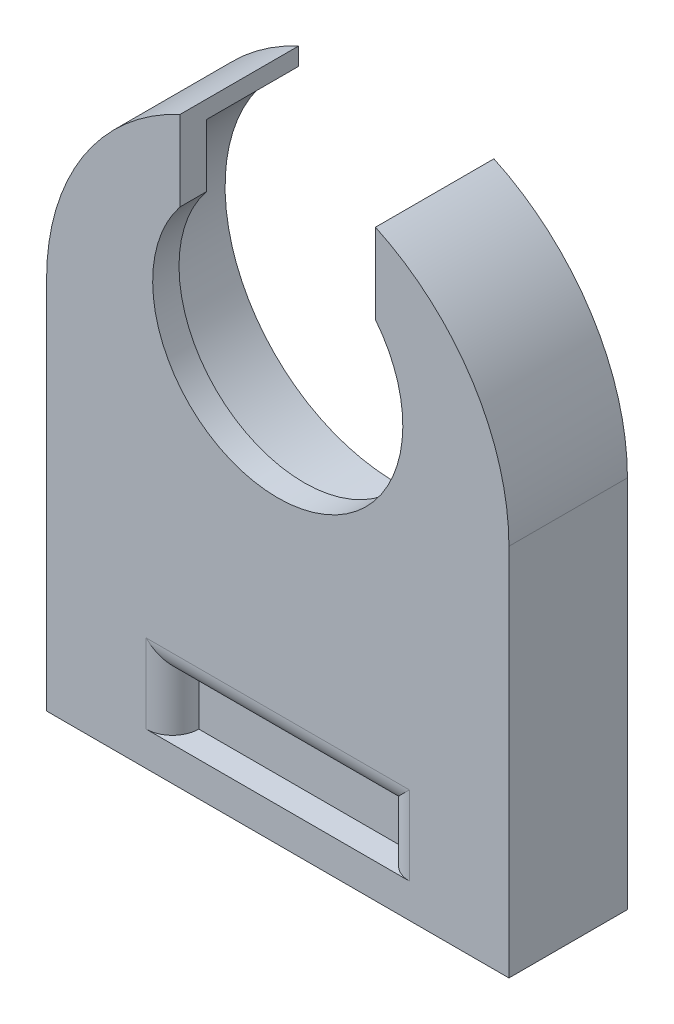
SolidWorks part; units mm, degrees
ref_plane "Front Plane" through (0, 0, 0) normal (0, 0, 1) x (1, 0, 0)
ref_plane "Top Plane" through (0, 0, 0) normal (0, 1, 0) x (1, 0, 0)
ref_plane "Right Plane" through (0, 0, 0) normal (1, 0, 0) x (0, 0, -1)
sketch "Sketch1" plane through (0, 0, 0) normal (0, 0, 1) x (1, 0, 0)
  line L0 (5.32, 14.0026) -> (5.32, 14.6195)
  line L1 (0, 0) -> (17.56, 0)
  line L2 (0, 0) -> (0, 6.55)
  line L3 (0, 6.55) -> (17.56, 6.55)
  line L4 (17.56, 0) -> (17.56, 6.55)
  line L6 (12.24, 14.0026) -> (12.24, 14.6195)
  arc A0 (5.32, 14.6195) -> (0, 6.55) centre (8.78, 6.55) ccw
  arc A1 (5.32, 14.0026) -> (12.24, 14.0026) centre (8.78, 8.5) ccw
  arc A2 (17.56, 6.55) -> (12.24, 14.6195) centre (8.78, 6.55) ccw
  dimension "D4" = 13
  dimension "D1" = 17.56
  dimension "D2" = 6.55
  dimension "D5" = 1.95
  dimension "D6" = 5.32
extrude "Boss-Extrude1" add sketch "Sketch1" along normal blind 3.5 contours A1 L3 L2 L1 L4 | A1 L0 A0 L3 | L3 A2 L6 A1 region at (1.98, 9.9073, 0) region at (8.78, 1.8126, 0) region at (15.58, 9.9073, 0)
sketch "Sketch3" plane through (0, 0, 3.5) normal (0, 0, 1) x (1, 0, 0)
  line L5 (5.32, 14.0026) -> (5.32, 14.6195)
  line L6 (0, 6.55) -> (0, 0)
  line L7 (0, 0) -> (17.56, 0)
  line L8 (17.56, 0) -> (17.56, 6.55)
  line L9 (12.24, 14.6195) -> (12.24, 14.0026)
  line L10 (5.32, 14.0026) -> (5.32, 14.6195)
  line L11 (0, 6.55) -> (0, 0)
  line L12 (0, 0) -> (17.56, 0)
  line L13 (17.56, 0) -> (17.56, 6.55)
  line L14 (12.24, 14.6195) -> (12.24, 14.0026)
  line L15 (0, 0) -> (17.56, 0)
  line L16 (17.56, 6.55) -> (17.56, 0)
  line L17 (0, 0) -> (0, 6.55)
  line L18 (5.32, 14.6195) -> (12.24, 14.6195)
  arc A3 (5.32, 14.0026) -> (12.24, 14.0026) centre (8.78, 8.5) ccw
  arc A4 (5.32, 14.6195) -> (0, 6.55) centre (8.78, 6.55) ccw
  arc A5 (17.56, 6.55) -> (12.24, 14.6195) centre (8.78, 6.55) ccw
  arc A6 (5.32, 14.0026) -> (12.24, 14.0026) centre (8.78, 8.5) ccw
  arc A7 (5.32, 14.6195) -> (0, 6.55) centre (8.78, 6.55) ccw
  arc A8 (17.56, 6.55) -> (12.24, 14.6195) centre (8.78, 6.55) ccw
  arc A9 (17.56, 6.55) -> (12.24, 14.6195) centre (8.78, 6.55) ccw
  arc A10 (0, 6.55) -> (5.32, 14.6195) centre (8.78, 6.55) cw
  arc M9 (12.24, 14.0026) -> (5.32, 14.0026) centre (8.78, 8.5) cw
  line M10 (5.32, 14.0026) -> (5.32, 14.6195)
  arc M11 (5.32, 14.6195) -> (0, 6.55) centre (8.78, 6.55) ccw
  line M12 (0, 6.55) -> (0, 0)
  line M13 (0, 0) -> (17.56, 0)
  line M14 (17.56, 0) -> (17.56, 6.55)
  arc M15 (17.56, 6.55) -> (12.24, 14.6195) centre (8.78, 6.55) ccw
  line M16 (12.24, 14.6195) -> (12.24, 14.0026)
  dimension "D1" = 0
extrude "Boss-Extrude2" add sketch "Sketch3" along normal blind 1 contours M16 M9 M10 M11 M12 M13 M14 M15 | L18 M10 M9 M16 region at (8.78, 1.7715, 3.5) region at (8.78, 8.4788, 3.5)
sketch "Sketch4" plane through (0, 0, 3.5) normal (0, 0, -1) x (-1, 0, 0)
  circle A0 centre (-8.78, 8.5) radius 4.75
  dimension "D1" = 9.5
extrude "Cut-Extrude1" cut sketch "Sketch4" against normal through all
sketch "Sketch5" plane through (0, 0, 0) normal (0, -1, 0) x (1, 0, 0)
  line L1 (0, 4.5) -> (17.56, 4.5)
  line L2 (0, 4.5) -> (0, 0)
  line L3 (0, 0) -> (17.56, 0)
  line L4 (17.56, 4.5) -> (17.56, 0)
extrude "Boss-Extrude3" add sketch "Sketch5" along normal blind 0.15
sketch "Sketch6" plane through (0, -0.15, 0) normal (0, -1, 0) x (1, 0, 0)
  line L4 (0, 4.5) -> (0, 0)
  line L5 (0, 0) -> (17.56, 0)
  line L6 (17.56, 0) -> (17.56, 4.5)
  line L7 (17.56, 4.5) -> (0, 4.5)
  line L8 (0, 4.5) -> (0, 0)
  line L9 (0, 0) -> (17.56, 0)
  line L10 (17.56, 0) -> (17.56, 4.5)
  line L11 (17.56, 4.5) -> (0, 4.5)
  dimension "D1" = 0
extrude "Boss-Extrude4" add sketch "Sketch6" along normal blind 7.5
sketch "Sketch9" plane through (0, 0, 4.5) normal (0, 0, 1) x (1, 0, 0)
  line L0 (12.78, -4.3532) -> (17.56, -4.3532) construction
  line L1 (12.78, -6.3532) -> (4.78, -6.3532)
  line L2 (12.78, -6.3532) -> (12.78, -4.3532)
  line L3 (12.78, -4.3532) -> (4.78, -4.3532)
  line L4 (4.78, -6.3532) -> (4.78, -4.3532)
  line L5 (17.56, -7.65) -> (17.56, 6.55) construction
  line L6 (4.78, -4.3532) -> (0, -4.3532) construction
  line L7 (0, 6.55) -> (0, -7.65) construction
  dimension "D1" = 2
  dimension "D2" = 8
extrude "Cut-Extrude2" cut sketch "Sketch9" against normal blind 1
fillet "Fillet1" radius 1 3 edges at (4.78, -5.3532, 4.5) (12.78, -5.3532, 4.5) (8.78, -4.3532, 4.5)
sketch "Sketch10" plane through (0, 14.6195, 0) normal (0, 1, 0) x (1, 0, 0)
  line L4 (12.24, -3.5) -> (5.32, -3.5)
  line L5 (5.32, -3.5) -> (5.32, -4.5)
  line L6 (5.32, -4.5) -> (12.24, -4.5)
  line L7 (12.24, -4.5) -> (12.24, -3.5)
  line L8 (12.24, -3.5) -> (5.32, -3.5)
  line L9 (5.32, -3.5) -> (5.32, -4.5)
  line L10 (5.32, -4.5) -> (12.24, -4.5)
  line L11 (12.24, -4.5) -> (12.24, -3.5)
  dimension "D1" = 0
extrude "Cut-Extrude3" cut sketch "Sketch10" against normal up to next
ref_plane "Plane1" through (8.78, 0, 0) normal (-1, 0, 0) x (0, 0, 1)
sketch "Sketch11" plane through (5.32, 0, 0) normal (1, 0, 0) x (0, 0, -1)
  line L1 (-4.5, 14.6195) -> (0, 14.6195)
  line L2 (-4.5, 14.6195) -> (-4.5, 11.0306)
  line L3 (-4.5, 11.0306) -> (0, 11.0306)
  line L4 (0, 14.6195) -> (0, 11.0306)
extrude "Cut-Extrude4" cut sketch "Sketch11" against normal blind 0.25
mirror "Mirror1" about plane through (8.78, 0, 0) normal (-1, 0, 0) of "Cut-Extrude4"
